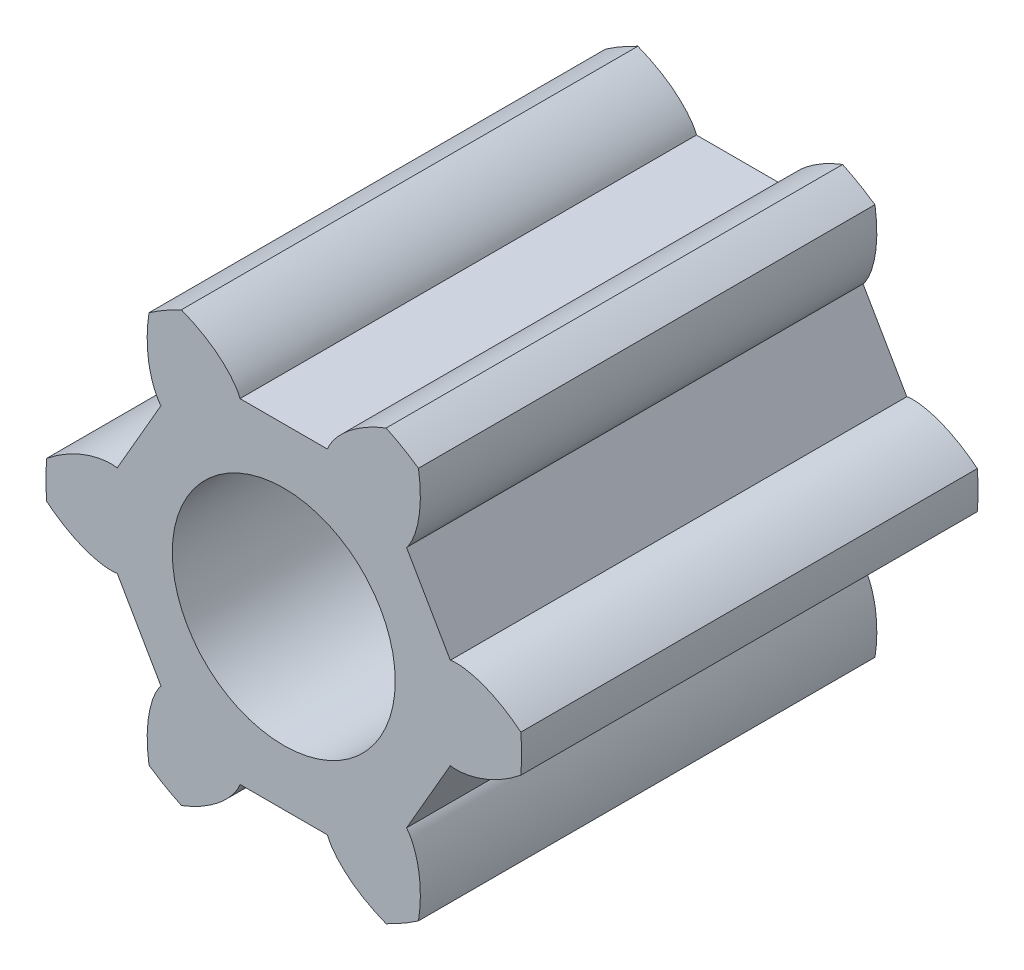
SolidWorks part; units mm, degrees
material "Brass"
ref_plane "Front Plane" through (0, 0, 0) normal (0, 0, 1) x (1, 0, 0)
ref_plane "Top Plane" through (0, 0, 0) normal (0, 1, 0) x (1, 0, 0)
ref_plane "Right Plane" through (0, 0, 0) normal (1, 0, 0) x (0, 0, -1)
sketch "Sketch1" plane through (0, 0, 0) normal (0, 0, 1) x (1, 0, 0)
  circle A0 centre (0, 0) radius 3.3867
  dimension "D1" = 6.7733
extrude "Boss-Extrude1" add sketch "Sketch1" along normal blind 6.5
sketch "Sketch2" plane through (0, 0, 0) normal (0, 0, 1) x (1, 0, 0)
  circle A0 centre (0, 0) radius 1.5875
  dimension "D1" = 3.175
extrude "Cut-Extrude2" cut sketch "Sketch2" against normal blind 8.5 and the other way blind 8.5
sketch "Sketch3" plane through (0, 0, 0) normal (0, 0, 1) x (1, 0, 0)
  spline S0 degree 4 poles (2.3717, 0.6496) (2.3733, 0.65) (2.3778, 0.651) (2.3917, 0.6536) (2.4195, 0.6567) (2.4541, 0.658) (2.494, 0.657) (2.5326, 0.654) (2.5656, 0.6502) (2.5984, 0.6454) (2.6311, 0.6395) (2.6705, 0.6311) (2.7176, 0.6194) (2.7723, 0.6034) (2.8338, 0.5823) (2.8958, 0.5579) (2.9563, 0.5314) (3.0165, 0.5019) (3.0742, 0.4714) (3.1331, 0.437) (3.187, 0.4038) (3.2462, 0.3636) (3.2936, 0.3303) (3.3546, 0.2833) (3.3902, 0.2547) (3.4314, 0.2201) (3.4494, 0.2042) (3.4605, 0.1944) knots 0 0 0 0 0 0.005377 0.015084 0.04661 0.092111 0.119476 0.146842 0.174209 0.201575 0.228941 0.256307 0.307035 0.361767 0.4165 0.471232 0.525964 0.580697 0.635429 0.690161 0.744894 0.799626 0.854358 0.909091 0.954545 1 1 1 1 1 construction
  spline S1 degree 4 poles (2.3717, 0.6496) (2.3733, 0.65) (2.3778, 0.651) (2.3917, 0.6536) (2.4195, 0.6567) (2.4541, 0.658) (2.494, 0.657) (2.5326, 0.654) (2.5656, 0.6502) (2.5984, 0.6454) (2.6311, 0.6395) (2.6705, 0.6311) (2.7176, 0.6194) (2.7723, 0.6034) (2.8338, 0.5823) (2.8958, 0.5579) (2.9563, 0.5314) (3.0165, 0.5019) (3.0742, 0.4714) (3.1331, 0.437) (3.187, 0.4038) (3.2462, 0.3636) (3.2936, 0.3303) (3.3414, 0.2935) (3.3645, 0.2753) (3.3762, 0.2658) knots 0 0 0 0 0 0.005377 0.015084 0.04661 0.092111 0.119476 0.146842 0.174209 0.201575 0.228941 0.256307 0.307035 0.361767 0.4165 0.471232 0.525964 0.580697 0.635429 0.690161 0.744894 0.799626 0.854358 0.909091 0.909091 0.909091 0.909091 0.909091
  spline S2 degree 4 poles (1.7485, 1.7292) (1.7496, 1.7303) (1.7527, 1.7337) (1.7618, 1.7445) (1.7785, 1.767) (1.7969, 1.7963) (1.816, 1.8314) (1.8327, 1.8663) (1.8459, 1.8967) (1.8581, 1.9276) (1.8693, 1.9589) (1.8818, 1.9972) (1.8953, 2.0438) (1.9087, 2.0992) (1.9212, 2.163) (1.9311, 2.2289) (1.9384, 2.2945) (1.9429, 2.3614) (1.9453, 2.4266) (1.945, 2.4949) (1.9432, 2.5582) (1.938, 2.6295) (1.9328, 2.6871) (1.9227, 2.7635) (1.9157, 2.8087) (1.9063, 2.8616) (1.9015, 2.8852) (1.8986, 2.8996) knots 0 0 0 0 0 0.005377 0.015084 0.04661 0.092111 0.119476 0.146842 0.174209 0.201575 0.228941 0.256307 0.307035 0.361767 0.4165 0.471232 0.525964 0.580697 0.635429 0.690161 0.744894 0.799626 0.854358 0.909091 0.954545 1 1 1 1 1 construction
  spline S3 degree 4 poles (1.7485, 1.7292) (1.7496, 1.7303) (1.7527, 1.7337) (1.7618, 1.7445) (1.7785, 1.767) (1.7969, 1.7963) (1.816, 1.8314) (1.8327, 1.8663) (1.8459, 1.8967) (1.8581, 1.9276) (1.8693, 1.9589) (1.8818, 1.9972) (1.8953, 2.0438) (1.9087, 2.0992) (1.9212, 2.163) (1.9311, 2.2289) (1.9384, 2.2945) (1.9429, 2.3614) (1.9453, 2.4266) (1.945, 2.4949) (1.9432, 2.5582) (1.938, 2.6295) (1.9328, 2.6871) (1.9249, 2.747) (1.9206, 2.7761) (1.9183, 2.791) knots 0 0 0 0 0 0.005377 0.015084 0.04661 0.092111 0.119476 0.146842 0.174209 0.201575 0.228941 0.256307 0.307035 0.361767 0.4165 0.471232 0.525964 0.580697 0.635429 0.690161 0.744894 0.799626 0.854358 0.909091 0.909091 0.909091 0.909091 0.909091
  spline S4 degree 4 poles (1.6858, 1.8377) (1.6906, 1.8294) (1.6999, 1.8133) (1.7114, 1.7933) (1.7423, 1.7398) (1.7557, 1.7167) (1.7917, 1.6542) (1.8139, 1.6158) (1.8445, 1.5628) (1.8705, 1.5178) (1.8989, 1.4685) (1.9249, 1.4236) (1.9522, 1.3764) (1.9783, 1.3311) (2.0079, 1.2798) (2.0377, 1.2281) (2.0687, 1.1745) (2.1004, 1.1196) (2.1318, 1.0651) (2.1643, 1.009) (2.1951, 0.9557) (2.228, 0.8985) (2.2566, 0.8491) (2.2929, 0.7861) (2.317, 0.7445) (2.3621, 0.6662) (2.3797, 0.6359) (2.4142, 0.5761) (2.4253, 0.5569) (2.4341, 0.5416) knots 0 0 0 0 0 0.022716 0.045432 0.083333 0.120011 0.156275 0.187738 0.22952 0.266865 0.306166 0.333066 0.372248 0.410428 0.447297 0.490604 0.53198 0.576487 0.615852 0.660543 0.702228 0.746442 0.783597 0.827286 0.872787 0.916667 0.958333 1 1 1 1 1 construction
  spline S5 degree 4 poles (1.7485, 1.7292) (1.7542, 1.7193) (1.7653, 1.7) (1.7917, 1.6542) (1.8139, 1.6158) (1.8445, 1.5628) (1.8705, 1.5178) (1.8989, 1.4685) (1.9249, 1.4236) (1.9522, 1.3764) (1.9783, 1.3311) (2.0079, 1.2798) (2.0377, 1.2281) (2.0687, 1.1745) (2.1004, 1.1196) (2.1318, 1.0651) (2.1643, 1.009) (2.1951, 0.9557) (2.228, 0.8985) (2.2566, 0.8491) (2.2929, 0.7861) (2.317, 0.7445) (2.3514, 0.6849) (2.3649, 0.6615) (2.3717, 0.6496) knots 0.083333 0.083333 0.083333 0.083333 0.083333 0.120011 0.156275 0.187738 0.22952 0.266865 0.306166 0.333066 0.372248 0.410428 0.447297 0.490604 0.53198 0.576487 0.615852 0.660543 0.702228 0.746442 0.783597 0.827286 0.872787 0.916667 0.916667 0.916667 0.916667 0.916667
  spline S6 degree 4 poles (-2.3293, -0.1834) (-2.0763, -0.1634) (-1.561, -0.1229) (-1.3586, -0.1069) (0.7061, 0.0556) (2.997, 0.2359) (5.2145, 0.4105) (10.5128, 0.8276) (13.8922, 1.0936) (18.4906, 1.4556) (21.8521, 1.7202) (25.4104, 2.0003) (28.3908, 2.235) (31.3575, 2.4685) (34.2899, 2.6994) (37.2152, 2.9296) (39.9163, 3.1423) (42.5147, 3.3468) (44.8278, 3.5289) (47.0637, 3.7049) (49.2392, 3.8762) (51.1721, 4.0284) (53.0077, 4.1729) (54.4743, 4.2883) (56.1221, 4.418) (57.3099, 4.5115) (59.3407, 4.6714) (60.3111, 4.7478) (62.4722, 4.9179) (63.3078, 4.9837) (64.6066, 5.0859) (65.0172, 5.1183) (65.3168, 5.1418) (65.4761, 5.1544) knots 0 0 0 0 0 0.010417 0.020833 0.041667 0.083333 0.149201 0.214066 0.274926 0.336786 0.387725 0.432177 0.474125 0.519126 0.559023 0.607792 0.645423 0.67943 0.712244 0.744224 0.778159 0.806538 0.828716 0.84913 0.870288 0.894043 0.916667 0.93842 0.968206 0.984103 0.992052 1 1 1 1 1 construction
  spline S7 degree 4 poles (3.3762, 0.2658) (4.3056, 0.3389) (6.161, 0.485) (10.5128, 0.8276) (13.8922, 1.0936) (18.4906, 1.4556) (21.8521, 1.7202) (25.4104, 2.0003) (28.3908, 2.235) (31.3575, 2.4685) (34.2899, 2.6994) (37.2152, 2.9296) (39.9163, 3.1423) (42.5147, 3.3468) (44.8278, 3.5289) (47.0637, 3.7049) (49.2392, 3.8762) (51.1721, 4.0284) (53.0077, 4.1729) (54.4743, 4.2883) (56.1221, 4.418) (57.3099, 4.5115) (58.8459, 4.6325) (59.4956, 4.6836) (59.8148, 4.7087) knots 0.083333 0.083333 0.083333 0.083333 0.083333 0.149201 0.214066 0.274926 0.336786 0.387725 0.432177 0.474125 0.519126 0.559023 0.607792 0.645423 0.67943 0.712244 0.744224 0.778159 0.806538 0.828716 0.84913 0.870288 0.894043 0.916667 0.916667 0.916667 0.916667 0.916667
  spline S8 degree 4 poles (59.9966, -0.6268) (59.9984, -0.4591) (60.0006, -0.1236) (60.0001, 0.3819) (59.9924, 1.0494) (59.9763, 1.727) (59.9548, 2.3767) (59.9216, 3.08) (59.891, 3.6556) (59.8317, 4.5009) (59.8007, 4.8957) (59.7298, 5.7097) (59.6721, 6.2716) (59.5999, 6.9315) (59.5241, 7.5513) (59.4403, 8.1863) (59.3504, 8.8137) (59.2294, 9.6) (59.071, 10.54) (58.8669, 11.6341) (58.6071, 12.8787) (58.3211, 14.1179) (58.0088, 15.3505) (57.5859, 16.8828) (57.0266, 18.7066) (56.2993, 20.8103) (55.367, 23.1771) (54.3352, 25.5023) (53.2058, 27.7817) (51.9808, 30.0112) (50.6626, 32.1867) (49.2531, 34.3046) (47.7557, 36.3605) (46.1715, 38.3517) (44.506, 40.2731) (42.7579, 42.1238) (41.1653, 43.6741) (39.7476, 44.9583) (38.5472, 45.9873) (37.5503, 46.8031) (36.5775, 47.5698) (35.6392, 48.2719) (34.9494, 48.7746) (34.1448, 49.3379) (33.8106, 49.5675) (33.1137, 50.0377) (32.6268, 50.3545) (32.0363, 50.7336) (31.4834, 51.0777) (30.9052, 51.4302) (30.3307, 51.7708) (29.8933, 52.0238) (29.6016, 52.1897) (29.4555, 52.272) knots 0 0 0 0 0 0.010479 0.020959 0.031438 0.041918 0.052272 0.062626 0.072979 0.083333 0.093254 0.103175 0.113095 0.123016 0.132937 0.142857 0.152778 0.162698 0.18254 0.202381 0.222222 0.242063 0.261905 0.281746 0.321429 0.361111 0.400794 0.440476 0.480159 0.519841 0.559524 0.599206 0.638889 0.678571 0.718254 0.757937 0.797619 0.81746 0.837302 0.857143 0.876984 0.896825 0.906746 0.916667 0.927021 0.937374 0.947728 0.958082 0.968562 0.979041 0.989521 1 1 1 1 1 construction
  spline S9 degree 4 poles (59.8148, 4.7087) (59.8044, 4.8408) (59.7824, 5.1058) (59.7298, 5.7097) (59.6721, 6.2716) (59.5999, 6.9315) (59.5241, 7.5513) (59.4403, 8.1863) (59.3504, 8.8137) (59.2294, 9.6) (59.071, 10.54) (58.8669, 11.6341) (58.6071, 12.8787) (58.3211, 14.1179) (58.0088, 15.3505) (57.5859, 16.8828) (57.0266, 18.7066) (56.2993, 20.8103) (55.367, 23.1771) (54.3352, 25.5023) (53.2058, 27.7817) (51.9808, 30.0112) (50.6626, 32.1867) (49.2531, 34.3046) (47.7557, 36.3605) (46.1715, 38.3517) (44.506, 40.2731) (42.7579, 42.1238) (41.1653, 43.6741) (39.7476, 44.9583) (38.5472, 45.9873) (37.5503, 46.8031) (36.5775, 47.5698) (35.6392, 48.2719) (34.9494, 48.7746) (34.3113, 49.2214) (34.0944, 49.3718) (33.9853, 49.4468) knots 0.083333 0.083333 0.083333 0.083333 0.083333 0.093254 0.103175 0.113095 0.123016 0.132937 0.142857 0.152778 0.162698 0.18254 0.202381 0.222222 0.242063 0.261905 0.281746 0.321429 0.361111 0.400794 0.440476 0.480159 0.519841 0.559524 0.599206 0.638889 0.678571 0.718254 0.757937 0.797619 0.81746 0.837302 0.857143 0.876984 0.896825 0.906746 0.916667 0.916667 0.916667 0.916667 0.916667
  spline S10 degree 4 poles (37.1986, 54.122) (37.131, 54.0237) (37.0037, 53.8384) (36.8621, 53.6324) (36.2211, 52.6998) (35.7565, 52.0238) (34.3765, 50.016) (33.7878, 49.1595) (32.3675, 47.0929) (31.3855, 45.6643) (29.9622, 43.5934) (28.7449, 41.8222) (27.3912, 39.8528) (26.1541, 38.0529) (24.9261, 36.2662) (23.5875, 34.3185) (22.2026, 32.3035) (20.7734, 30.2241) (19.2552, 28.0153) (17.7523, 25.8287) (16.0393, 23.3363) (14.3391, 20.8626) (12.2867, 17.8765) (10.3801, 15.1025) (7.7962, 11.3431) (5.9421, 8.6455) (2.9325, 4.2666) (1.6989, 2.4718) (0.3887, 0.5656) (-0.7703, -1.1207) (-0.8681, -1.263) (-1.2155, -1.7685) (-1.3053, -1.8992) knots 0 0 0 0 0 0.00584 0.01168 0.02336 0.049866 0.083333 0.107823 0.134866 0.164138 0.204327 0.242901 0.269865 0.300063 0.335537 0.368815 0.410357 0.442859 0.485377 0.52489 0.569261 0.616561 0.669471 0.726012 0.78756 0.852113 0.916667 0.958333 0.979167 0.989583 1 1 1 1 1 construction
  spline S11 degree 4 poles (33.9853, 49.4468) (33.789, 49.1612) (33.3718, 48.5542) (32.3675, 47.0929) (31.3855, 45.6643) (29.9622, 43.5934) (28.7449, 41.8222) (27.3912, 39.8528) (26.1541, 38.0529) (24.9261, 36.2662) (23.5875, 34.3185) (22.2026, 32.3035) (20.7734, 30.2241) (19.2552, 28.0153) (17.7523, 25.8287) (16.0393, 23.3363) (14.3391, 20.8626) (12.2867, 17.8765) (10.3801, 15.1025) (7.7962, 11.3431) (5.9421, 8.6455) (3.4723, 5.052) (2.4358, 3.5439) (1.9183, 2.791) knots 0.083333 0.083333 0.083333 0.083333 0.083333 0.107823 0.134866 0.164138 0.204327 0.242901 0.269865 0.300063 0.335537 0.368815 0.410357 0.442859 0.485377 0.52489 0.569261 0.616561 0.669471 0.726012 0.78756 0.852113 0.916667 0.916667 0.916667 0.916667 0.916667
extrude "Cut-Extrude4" cut sketch "Sketch3" against normal blind 7.5 and the other way blind 7.5
ref_axis "Axis1" through (0, 0, -0.325) along (0, 0, 1)
pattern_circular "CirPattern1" count 6 over 360 about axis through (0, 0, -0.325) along (0, 0, 1) of "Cut-Extrude4"
equation "\"TrigProbe\"= cos(60)"
equation "\"SqrProbe\"= sqr(2)"
equation "\"AtnProbe\"= atn(1)"
equation "\"ToothCount\"= 6"
equation "\"DP\"= 30"
equation "\"PA\"= 14.5"
equation "\"PArad\"= \"PA\" * 3.14159265358979 / 180"
equation "\"Rb\"= \"ToothCount\" / \"DP\" * cos(\"PA\") / 2"
equation "\"Ra\"= (\"ToothCount\" + 2) / \"DP\" / 2"
equation "\"Tmax\"= sqr(\"Ra\" * \"Ra\" / (\"Rb\" * \"Rb\") - 1)"
equation "\"Delta\"= 3.14159265358979 / (2 * \"ToothCount\") + tan(\"PA\") - \"PArad\""
equation "\"Gamma\"= 2 * 3.14159265358979 / \"ToothCount\""
equation "\"ThetaL\"= atn(\"Tmax\") * 3.14159265358979 / 180 - \"Tmax\" + \"Delta\""
equation "\"ThetaU\"= \"Tmax\" - atn(\"Tmax\") * 3.14159265358979 / 180 - \"Delta\" + \"Gamma\""
equation "\"D1@Sketch1\" = 2 * \"Ra\""
equation "\"BoreDia\"= 0.125"
equation "\"D1@Sketch2\" = \"BoreDia\""
equation "\"D1@CirPattern1\" = \"ToothCount\""
